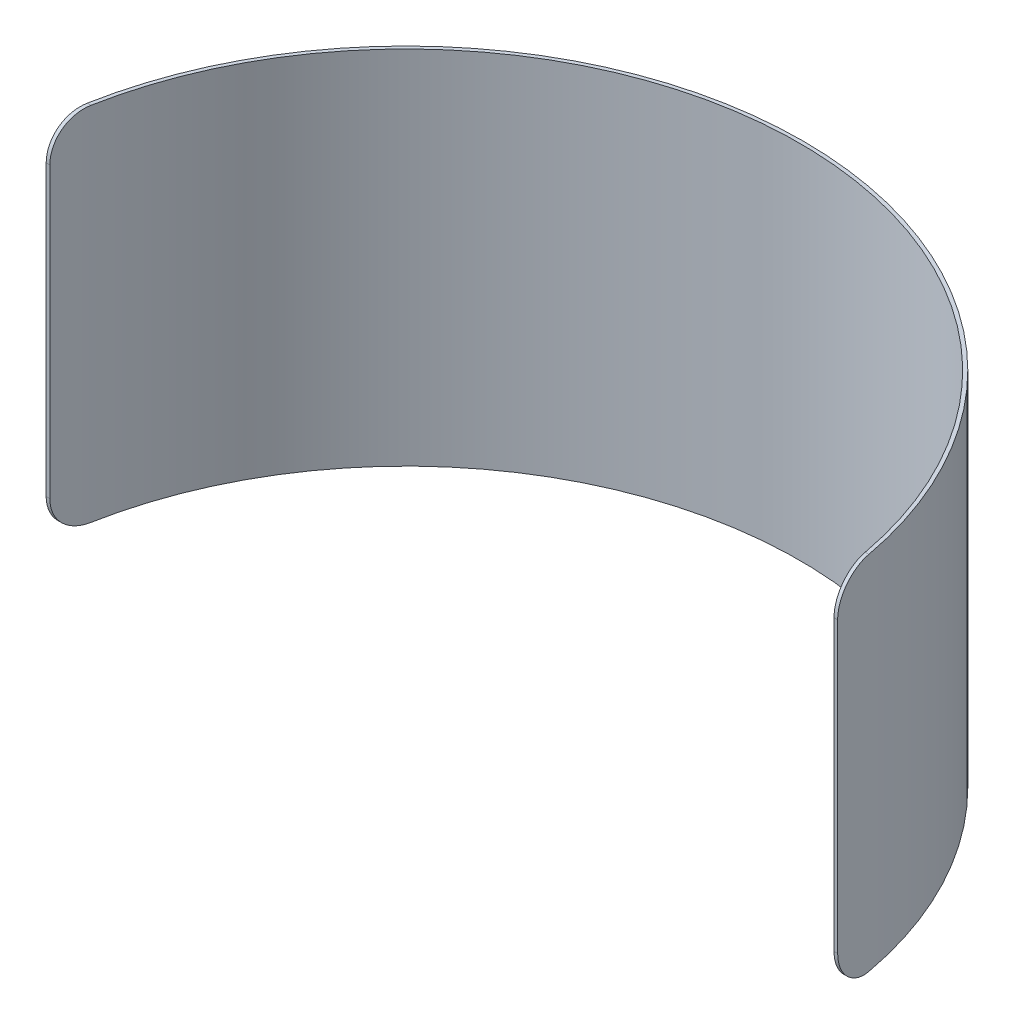
SolidWorks part; units mm, degrees
ref_plane "Front Plane" through (0, 0, 0) normal (0, 0, 1) x (1, 0, 0)
ref_plane "Top Plane" through (0, 0, 0) normal (0, 1, 0) x (1, 0, 0)
ref_plane "Right Plane" through (0, 0, 0) normal (1, 0, 0) x (0, 0, -1)
sketch "Sketch1" plane through (0, 0, 0) normal (0, 1, 0) x (1, 0, 0)
  line L0 (0, 0) -> (10.042, 0)
  line L1 (2190.89, 0) -> (2180.848, 0)
  arc A0 (0, 0) -> (2190.89, 0) centre (1095.445, -100.0013) cw
  arc A1 (10.042, 0) -> (2180.848, 0) centre (1095.445, -100.0013) cw
  arc A2 (9.9586, -0.9091) -> (2180.9314, -0.9091) centre (1095.445, -100.0013) cw construction
  dimension "D2" = 1100
  dimension "D1" = 2190.89
  dimension "D3" = 10
extrude "Boss-Extrude1" add sketch "Sketch1" along normal blind 1000
fillet "Fillet1" radius 100 4 edges at (2185.869, 1000, 0) (2185.869, 0, 0) (5.021, 0, 0) (5.021, 1000, 0)
